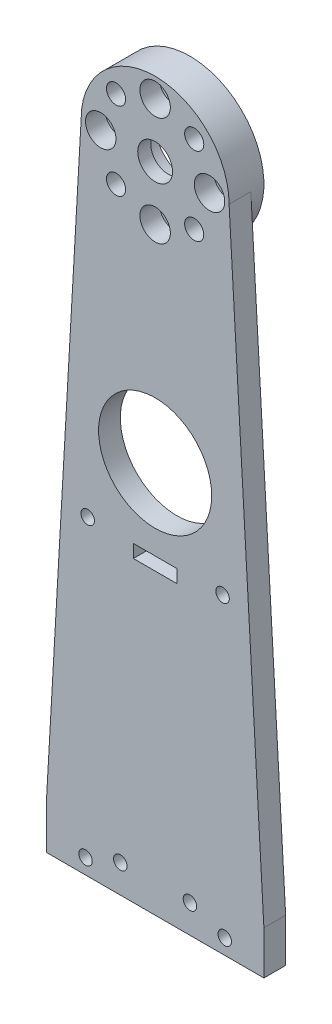
SolidWorks part; units mm, degrees
ref_plane "Front Plane" through (0, 0, 0) normal (0, 0, 1) x (1, 0, 0)
ref_plane "Top Plane" through (0, 0, 0) normal (0, 1, 0) x (1, 0, 0)
ref_plane "Right Plane" through (0, 0, 0) normal (1, 0, 0) x (0, 0, -1)
sketch "Sketch1" plane through (0, 0, 0) normal (0, 0, 1) x (1, 0, 0)
  line L0 (-25, 0) -> (25, 0)
  line L1 (0, 0) -> (0, 150) construction
  line L4 (0, 150) -> (0, 90) construction
  line L6 (-25, 0) -> (-25, 10)
  line L8 (25, 10) -> (25, 0)
  line L9 (-17, 150) -> (-25, 10)
  line L10 (17, 150) -> (25, 10)
  line L11 (-25, 0) -> (-25, 3.5) construction
  line L12 (-25, 3.5) -> (-16, 3.5) construction
  line L13 (-16, 3.5) -> (16, 3.5) construction
  line L14 (-25, 10) -> (-25, 6.5) construction
  line L15 (-25, 6.5) -> (-8, 6.5) construction
  line L16 (-8, 6.5) -> (8, 6.5) construction
  line L17 (0, 90) -> (0, 71.5) construction
  line L20 (-5, 68.5) -> (-15.5, 68.5) construction
  line L21 (5, 68.5) -> (5, 71.5) construction
  line L22 (5, 68.5) -> (-5, 68.5)
  line L23 (-5, 68.5) -> (-5, 71.5)
  line L24 (-5, 71.5) -> (5, 71.5)
  line L25 (5, 71.5) -> (5, 68.5)
  line L26 (-15.5, 68.5) -> (-15.5, 71.5) construction
  line L27 (5, 68.5) -> (15.5, 68.5) construction
  line L28 (15.5, 68.5) -> (15.5, 71.5) construction
  circle A0 centre (0, 150) radius 4
  arc A1 (-17, 150) -> (17, 150) centre (0, 150) cw
  circle A2 centre (0, 90) radius 13
  circle A3 centre (-8, 6.5) radius 1.55
  circle A4 centre (-16, 3.5) radius 1.55
  circle A5 centre (8, 6.5) radius 1.55
  circle A6 centre (16, 3.5) radius 1.55
  circle A7 centre (-15.5, 71.5) radius 1.55
  circle A8 centre (15.5, 71.5) radius 1.55
  point P4 (0, 0)
  point P29 (0, 71.5)
  point P30 (0, 71.5)
extrude "Boss-Extrude1" add sketch "Sketch1" along normal blind 5
sketch "Sketch2" plane through (0, 0, 0) normal (0, 0, -1) x (-1, 0, 0)
  circle A0 centre (0, 150) radius 17
extrude "Boss-Extrude2" add sketch "Sketch2" along normal blind 3
sketch "Sketch3" plane through (0, 0, 5) normal (0, 0, 1) x (1, 0, 0)
  line L0 (0, 150) -> (8.9803, 158.9803) construction
  circle A0 centre (0, 150) radius 12.5 construction
  circle A1 centre (-12.5, 150) radius 1.55
  circle A2 centre (0, 162.5) radius 1.55
  circle A3 centre (12.5, 150) radius 1.55
  circle A4 centre (0, 137.5) radius 1.55
  circle A5 centre (0, 150) radius 12.7 construction
  circle A6 centre (8.9803, 158.9803) radius 1
  circle A7 centre (8.9803, 141.0197) radius 1
  circle A8 centre (-8.9803, 141.0197) radius 1
  circle A9 centre (-8.9803, 158.9803) radius 1
  point P14 (0, 150)
  point P24 (0, 150)
  dimension "D1" = 4
  dimension "D2" = 4
extrude "Cut-Extrude1" cut sketch "Sketch3" against normal blind 8
sketch "Sketch4" plane through (0, 0, 5) normal (0, 0, 1) x (1, 0, 0)
  circle A0 centre (-12.5, 150) radius 3.5
  circle A1 centre (0, 162.5) radius 3.5
  circle A2 centre (12.5, 150) radius 3.5
  circle A3 centre (0, 137.5) radius 3.5
  circle A4 centre (-8.9803, 158.9803) radius 2.2
  circle A5 centre (8.9803, 158.9803) radius 2.2
  circle A6 centre (8.9803, 141.0197) radius 2.2
  circle A7 centre (-8.9803, 141.0197) radius 2.2
  point P12 (0, 150)
  point P22 (0, 150)
  dimension "D1" = 4
  dimension "D2" = 4
extrude "Cut-Extrude2" cut sketch "Sketch4" against normal blind 4.5
sketch "Sketch5" plane through (0, 0, -3) normal (0, 0, -1) x (-1, 0, 0)
  circle A0 centre (0, 150) radius 8.2
extrude "Cut-Extrude3" cut sketch "Sketch5" against normal blind 5
